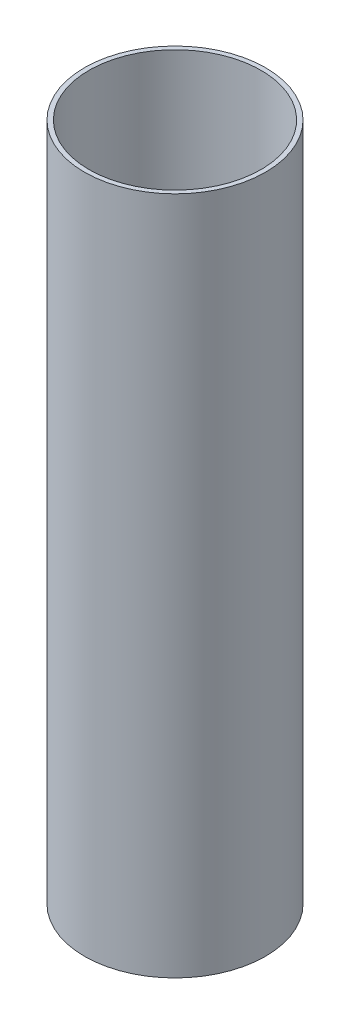
SolidWorks part; units mm, degrees
ref_plane "Front Plane" through (0, 0, 0) normal (0, 0, 1) x (1, 0, 0)
ref_plane "Top Plane" through (0, 0, 0) normal (0, 1, 0) x (1, 0, 0)
ref_plane "Right Plane" through (0, 0, 0) normal (1, 0, 0) x (0, 0, -1)
sketch "Sketch1" plane through (0, 0, 0) normal (0, 1, 0) x (1, 0, 0)
  circle A0 centre (0, 0) radius 38
  circle A1 centre (0, 0) radius 40
  dimension "D1" = 80
  dimension "D2" = 2
extrude "Boss-Extrude1" add sketch "Sketch1" along normal blind 300
